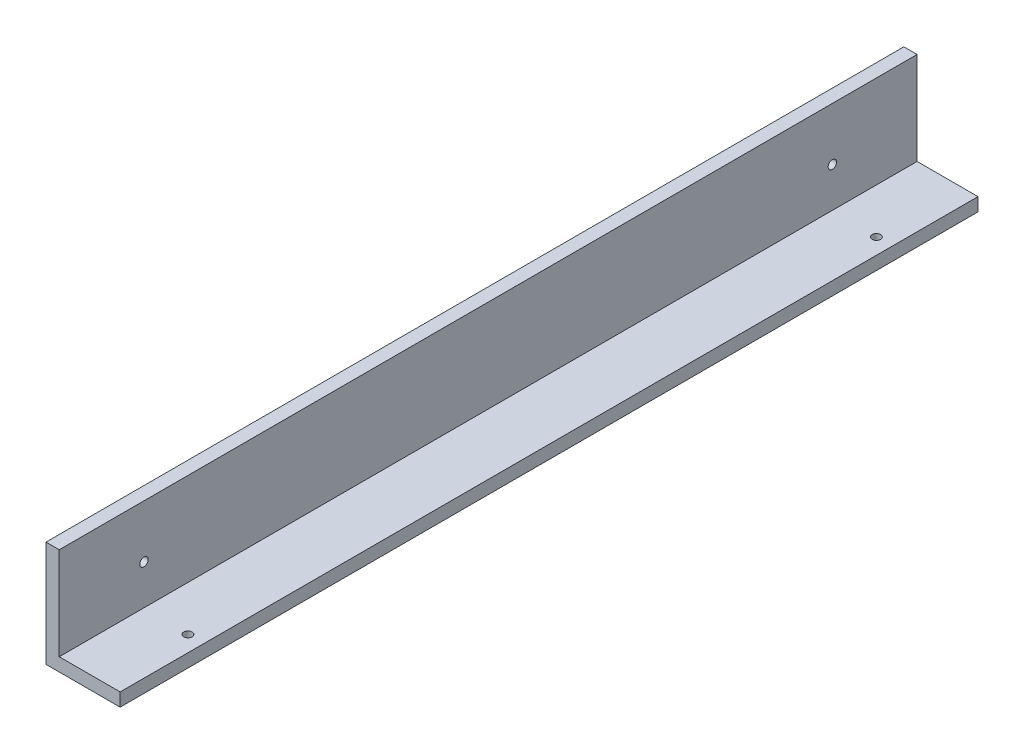
SolidWorks part; units mm, degrees
ref_plane "Front Plane" through (0, 0, 0) normal (0, 0, 1) x (1, 0, 0)
ref_plane "Top Plane" through (0, 0, 0) normal (0, 1, 0) x (1, 0, 0)
ref_plane "Right Plane" through (0, 0, 0) normal (1, 0, 0) x (0, 0, -1)
sketch "Sketch1" plane through (0, 0, 0) normal (0, 0, 1) x (1, 0, 0)
  line L0 (0, 0) -> (0, 50.8)
  line L1 (0, 0) -> (35.56, 0)
  line L2 (35.56, 0) -> (35.56, 6.35)
  line L3 (0, 50.8) -> (6.35, 50.8)
  line L4 (6.35, 50.8) -> (6.35, 6.35)
  line L5 (6.35, 6.35) -> (35.56, 6.35)
extrude "Boss-Extrude1" add sketch "Sketch1" along normal blind 411.48
sketch "Sketch7" plane through (0, 6.35, 0) normal (0, 1, 0) x (1, 0, 0)
  line L3 (27.94, -41.1353) -> (27.94, -371.3353) construction
hole_wizard "#10-32 Tapped Hole5" positions "Sketch14" profile "Sketch13" tap size "#10-32" standard "Ansi Inch" end condition through all
sketch "Sketch14" plane through (6.35, 0, 0) normal (1, 0, 0) x (0, 0, -1)
  line L5 (-411.48, 50.8) -> (-411.48, 25.4) construction
  line L6 (-411.48, 6.35) -> (-411.48, 50.8) construction
  line L8 (-411.48, 25.4) -> (-370.84, 25.4) construction
  point P0 (-370.84, 25.4)
sketch "Sketch13" plane through (6.35, 25.4, 370.84) normal (0, 1, 0) x (0, 0, -1)
  line L0 (0, 0) -> (0, 6.35)
  line L1 (0, 6.35) -> (2.0193, 6.35)
  line L2 (2.0193, 6.35) -> (2.0193, 0)
  line L5 (2.0193, 0) -> (0, 0)
  line L11 (0, -6.35) -> (0, 107.95) construction
  dimension "Thru Tap Drill Dia." = 4.0386
  dimension "Thru Tap Drill Depth" = 6.35
cosmetic thread "Hole Thread8"
hole_wizard "#10-32 Tapped Hole6" positions "Sketch16" profile "Sketch15" tap size "#10-32" standard "Ansi Inch" end condition through all
sketch "Sketch16" plane through (6.35, 0, 0) normal (1, 0, 0) x (0, 0, -1)
  line L0 (0, 50.8) -> (0, 25.4) construction
  line L1 (0, 6.35) -> (0, 50.8) construction
  line L2 (0, 25.4) -> (-40.64, 25.4) construction
  point P0 (-40.64, 25.4)
sketch "Sketch15" plane through (6.35, 25.4, 40.64) normal (0, 1, 0) x (0, 0, -1)
  line L0 (0, 0) -> (0, 6.35)
  line L1 (0, 6.35) -> (2.0193, 6.35)
  line L2 (2.0193, 6.35) -> (2.0193, 0)
  line L5 (2.0193, 0) -> (0, 0)
  line L11 (0, -6.35) -> (0, 107.95) construction
  dimension "Thru Tap Drill Dia." = 4.0386
  dimension "Thru Tap Drill Depth" = 6.35
cosmetic thread "Hole Thread9"
hole_wizard "#10-32 Tapped Hole7" positions "Sketch18" profile "Sketch17" tap size "#10-32" standard "Ansi Inch"
sketch "Sketch18" plane through (0, 6.35, 0) normal (0, 1, 0) x (-1, 0, 0)
  point P0 (-27.94, 41.1353)
sketch "Sketch17" plane through (27.94, 6.35, 41.1353) normal (1, 0, 0) x (0, 0, 1)
  line L0 (0, 0) -> (0, 13.1513)
  line L1 (0, 13.1513) -> (2.0193, 11.938)
  line L2 (2.0193, 11.938) -> (2.0193, 0)
  line L5 (2.0193, 0) -> (0, 0)
  line L10 (0, 13.1513) -> (-2.0193, 11.938) construction
  line L11 (0, -6.35) -> (0, 107.95) construction
  dimension "Tap Drill Dia." = 4.0386
  dimension "Tap Drill Depth" = 11.938
  dimension "Drill Angle" = 118
cosmetic thread "Hole Thread10"
hole_wizard "#10-32 Tapped Hole8" positions "Sketch20" profile "Sketch19" tap size "#10-32" standard "Ansi Inch"
sketch "Sketch20" plane through (0, 6.35, 0) normal (0, 1, 0) x (-1, 0, 0)
  point P0 (-27.94, 371.3353)
sketch "Sketch19" plane through (27.94, 6.35, 371.3353) normal (1, 0, 0) x (0, 0, 1)
  line L0 (0, 0) -> (0, 13.1513)
  line L1 (0, 13.1513) -> (2.0193, 11.938)
  line L2 (2.0193, 11.938) -> (2.0193, 0)
  line L5 (2.0193, 0) -> (0, 0)
  line L10 (0, 13.1513) -> (-2.0193, 11.938) construction
  line L11 (0, -6.35) -> (0, 107.95) construction
  dimension "Tap Drill Dia." = 4.0386
  dimension "Tap Drill Depth" = 11.938
  dimension "Drill Angle" = 118
cosmetic thread "Hole Thread11"
